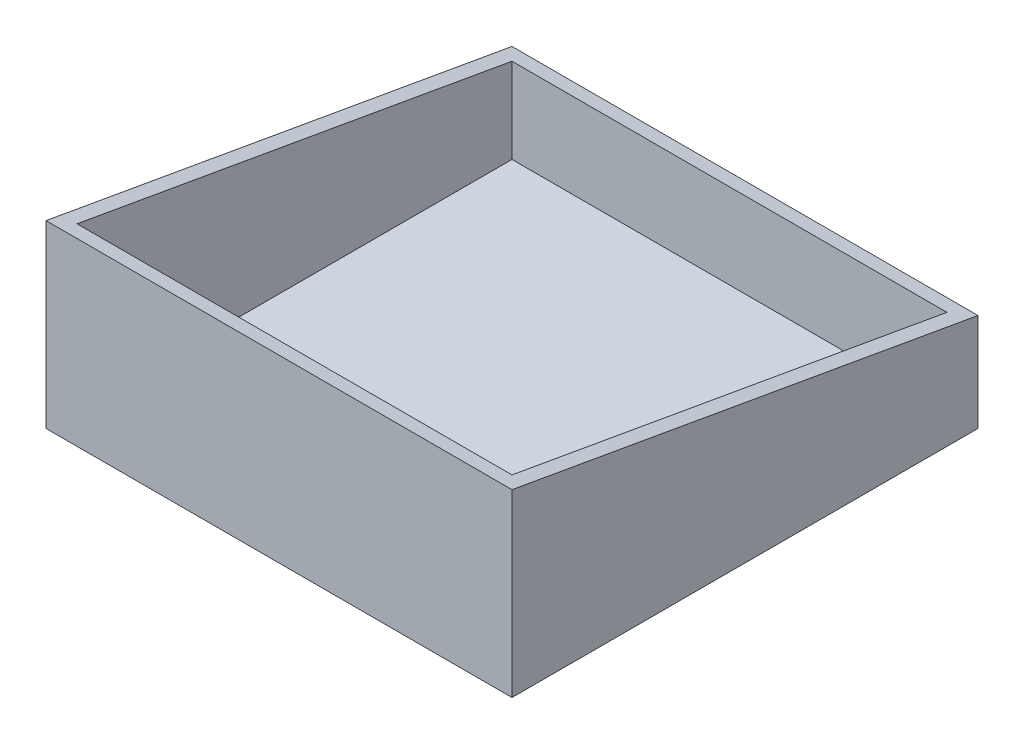
SolidWorks part; units mm, degrees
ref_plane "Front Plane" through (0, 0, 0) normal (0, 0, 1) x (1, 0, 0)
ref_plane "Top Plane" through (0, 0, 0) normal (0, 1, 0) x (1, 0, 0)
ref_plane "Right Plane" through (0, 0, 0) normal (1, 0, 0) x (0, 0, -1)
sketch "Sketch1" plane through (0, 0, 0) normal (1, 0, 0) x (0, 0, -1)
  line L1 (0, 0) -> (381, 0)
  line L4 (381, 0) -> (381, 80)
  line L5 (0, 147.1806) -> (381, 80)
  line L6 (0, 147.1806) -> (0, 0)
  dimension "D1" = 381
  dimension "D2" = 10
  dimension "D3" = 80
extrude "Boss-Extrude1" add sketch "Sketch1" along normal blind 381
shell "Shell1" thickness 12.7 removed face at (190.5, 113.5903, -190.5)
